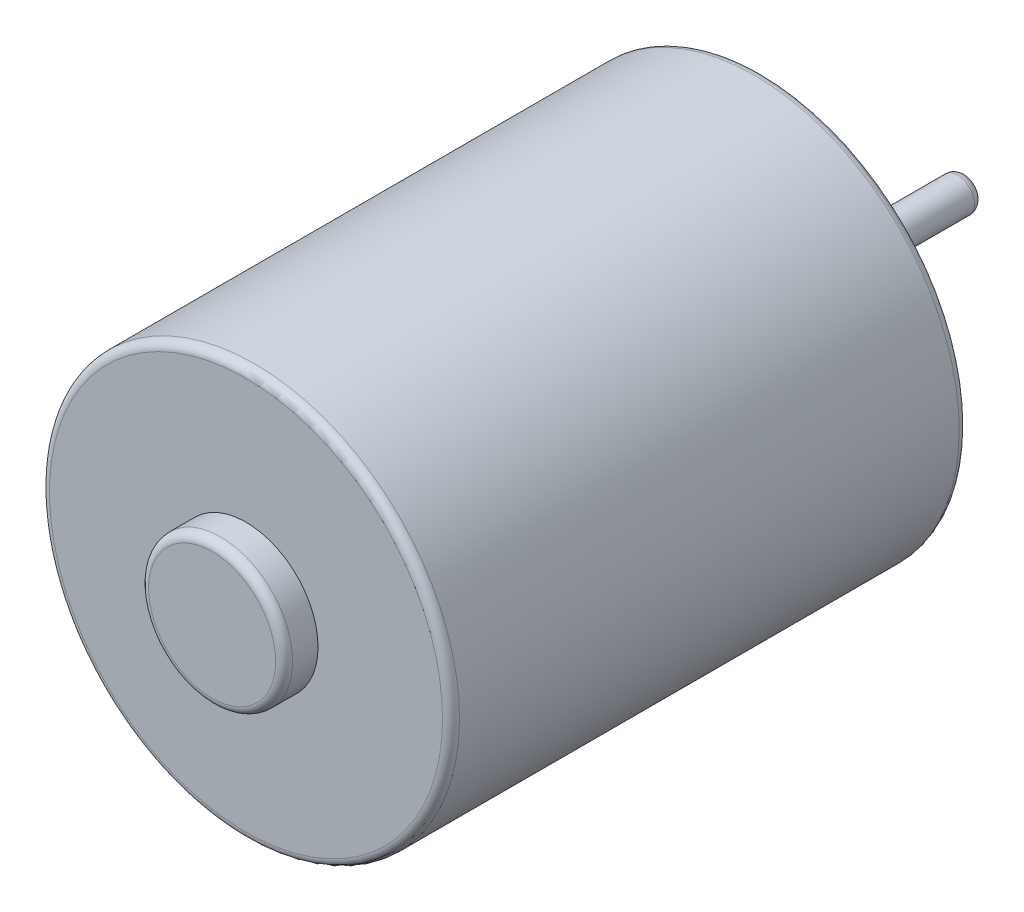
SolidWorks part; units mm, degrees
ref_plane "Front Plane" through (0, 0, 0) normal (0, 0, 1) x (1, 0, 0)
ref_plane "Top Plane" through (0, 0, 0) normal (0, 1, 0) x (1, 0, 0)
ref_plane "Right Plane" through (0, 0, 0) normal (1, 0, 0) x (0, 0, -1)
sketch "Sketch1" plane through (0, 0, 0) normal (0, 0, 1) x (1, 0, 0)
  circle A0 centre (0, 0) radius 12.1
  circle A1 centre (0, 0) radius 3.175
  circle A2 centre (0, 0) radius 1
  dimension "D1" = 24.2
  dimension "D2" = 6.35
  dimension "D3" = 2
extrude "Boss-Extrude1" add sketch "Sketch1" along normal blind 30.5 contours A1 A2 | A2 | A0 A1 region at (-11.7578, 0, 0) region at (-3.0852, 0, 0) region at (0, 0, 0)
extrude "Boss-Extrude2" add sketch "Sketch1<3>" against normal blind 12 contours A2 region at (0, 0, 0)
sketch "Sketch1<3>" plane through (0, 0, 0) normal (0, 0, 1) x (1, 0, 0) same geometry as "Sketch1"
extrude "Boss-Extrude3" add sketch "Sketch1<4>" against normal blind 1.6 contours A1 A2 region at (-3.0852, 0, 0)
sketch "Sketch1<4>" plane through (0, 0, 0) normal (0, 0, 1) x (1, 0, 0) same geometry as "Sketch1"
sketch "Sketch2" plane through (0, 0, 30.5) normal (0, 0, 1) x (1, 0, 0)
  circle A0 centre (0, 0) radius 4.25
  dimension "D1" = 8.5
extrude "Boss-Extrude4" add sketch "Sketch2" along normal blind 2
fillet "Fillet1" radius 0.5 5 edges at (1, 0, -12) (3.175, 0, -1.6) (12.1, 0, 0) (4.25, 0, 32.5) (12.1, 0, 30.5)
